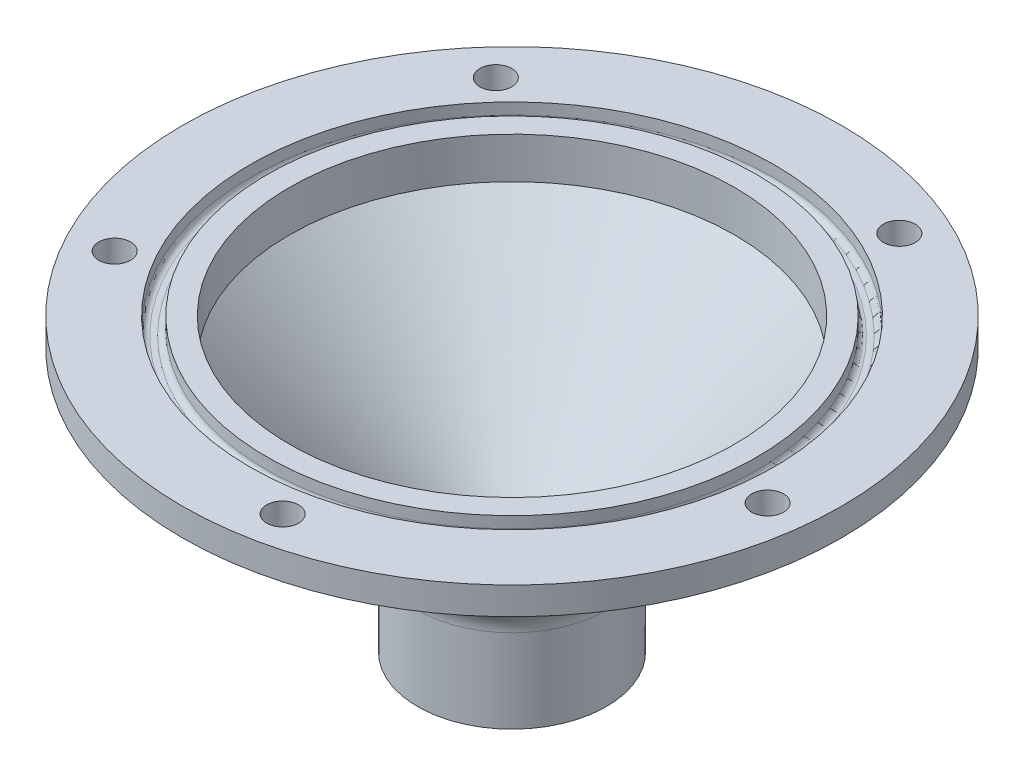
SolidWorks part; units mm, degrees
ref_plane "Front Plane" through (0, 0, 0) normal (0, 0, 1) x (1, 0, 0)
ref_plane "Top Plane" through (0, 0, 0) normal (0, 1, 0) x (1, 0, 0)
ref_plane "Right Plane" through (0, 0, 0) normal (1, 0, 0) x (0, 0, -1)
sketch "Sketch1" plane through (0, 0, 0) normal (0, 0, 1) x (1, 0, 0)
  line L0 (0, 0) -> (0, 76.2) construction
  line L1 (5.5562, 0) -> (5.5562, 8.1008)
  line L2 (5.5562, 8.1008) -> (20.574, 23.1185)
  line L3 (20.574, 26.9243) -> (22.6304, 26.9243)
  line L4 (30.48, 26.9243) -> (30.48, 24.3843)
  line L5 (30.48, 24.3843) -> (25.4, 24.3843)
  line L6 (23.1549, 23.4544) -> (9.6612, 9.9607)
  line L7 (8.7312, 7.7156) -> (8.7312, 0)
  line L8 (8.7312, 0) -> (5.5562, 0)
  line L9 (20.574, 23.1185) -> (20.574, 26.9243)
  line L10 (22.6304, 26.9243) -> (22.6304, 25.8766)
  line L11 (23.1702, 25.3368) -> (23.6782, 25.3368)
  line L12 (24.2179, 25.8766) -> (24.2179, 26.9243)
  line L13 (24.2179, 26.9243) -> (30.48, 26.9243)
  line L14 (-20.5296, 26.9243) -> (20.5296, 26.9243) construction
  arc A0 (9.6612, 9.9607) -> (8.7312, 7.7156) centre (11.9062, 7.7156) ccw
  arc A1 (25.4, 24.3843) -> (23.1549, 23.4544) centre (25.4, 21.2093) ccw
  arc A4 (23.6782, 25.3368) -> (24.2179, 25.8766) centre (23.6782, 25.8766) ccw
  arc A5 (22.6304, 25.8766) -> (23.1702, 25.3368) centre (23.1702, 25.8766) ccw
  point P16 (24.0849, 24.3843)
  point P28 (24.2179, 25.3368)
  dimension "D13" = 3.175
  dimension "D17" = 0.5397
  dimension "D8" = 3.175
  dimension "D1" = 76.2
  dimension "D2" = 3.175
  dimension "D3" = 1.5875
  dimension "D4" = 2.54
  dimension "D5" = 11.1125
  dimension "D6" = 45
  dimension "D7" = 30.48
  dimension "D9" = 5.08
  dimension "D14" = 1.5875
  dimension "D15" = 1.5875
revolve "Revolve1" add sketch "Sketch1" angle 360 about L0
sketch "Sketch2" plane through (0, 26.9243, 0) normal (0, 1, 0) x (1, 0, 0)
  circle A0 centre (-19.8166, 18.3201) radius 1.4732
  circle A1 centre (-19.8166, 18.3201) radius 1.4732 construction
extrude "Cut-Extrude1" cut sketch "Sketch2" against normal blind 2.54
sketch "Sketch3" plane through (0, 26.9243, 0) normal (0, 1, 0) x (1, 0, 0)
  circle A0 centre (-23.5471, -13.1855) radius 1.4732
  circle A1 centre (5.2637, -26.4692) radius 1.4732
  circle A2 centre (26.8003, -3.1734) radius 1.4732
  circle A3 centre (11.2998, 24.5079) radius 1.4732
  circle A4 centre (11.2998, 24.5079) radius 1.4732 construction
  circle A5 centre (26.8003, -3.1734) radius 1.4732 construction
  circle A6 centre (5.2637, -26.4692) radius 1.4732 construction
  circle A7 centre (-23.5471, -13.1855) radius 1.4732 construction
extrude "Cut-Extrude2" cut sketch "Sketch3" against normal through all
